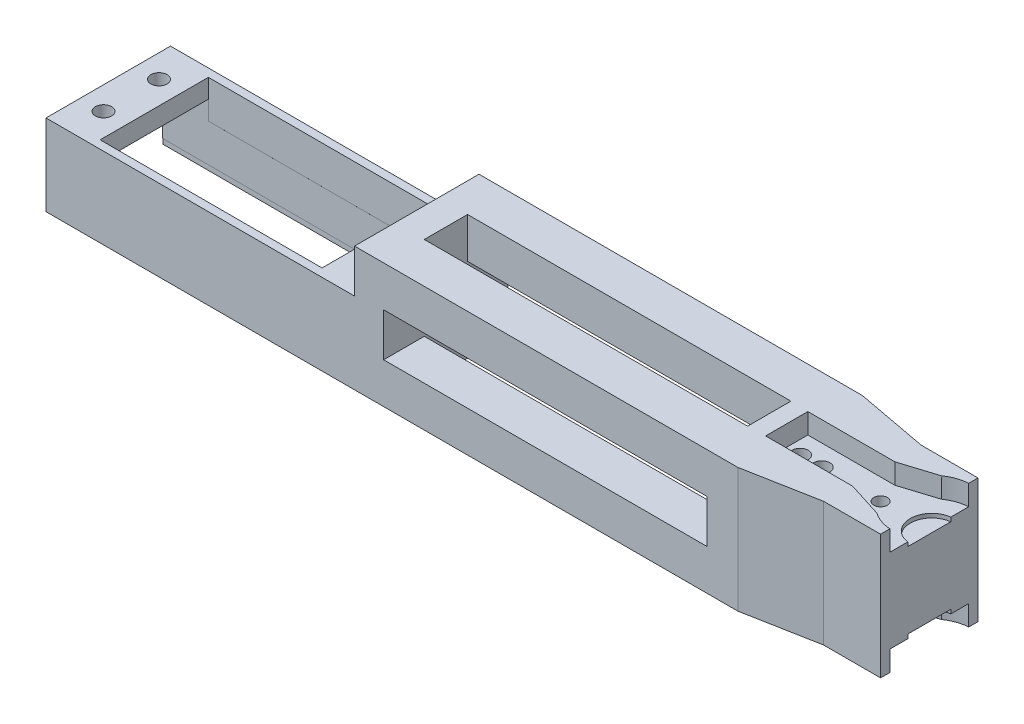
SolidWorks part; units mm, degrees
note: The reader was unsure of these and kept them because the rebuilt part matched: shared geometry of "Sketch1<13>", "Sketch1<14>", "Sketch9<12>".
ref_plane "Front Plane" through (0, 0, 0) normal (0, 0, 1) x (1, 0, 0)
ref_plane "Top Plane" through (0, 0, 0) normal (0, 1, 0) x (1, 0, 0)
ref_plane "Right Plane" through (0, 0, 0) normal (1, 0, 0) x (0, 0, -1)
sketch "Sketch1" plane through (0, 0, 0) normal (0, 1, 0) x (1, 0, 0)
  line L0 (0, 0) -> (14.6038, 0) construction
  line L1 (14.6038, 0) -> (-20.0982, 0) construction
  line L2 (14.6038, -7.2) -> (14.6038, 7.2) construction
  line L3 (-661.2792, -270.937) -> (-113.9458, -270.937) construction
  line L4 (3.082, 5.9567) -> (3.082, -8.253) construction
  line L5 (-17.0385, 7.2) -> (-17.0385, 4.8714) construction
  line L6 (-13.0385, 7.2) -> (-13.0385, 4.8714) construction
  line L7 (6.8243, 9.0002) -> (6.8243, -9.0002)
  line L8 (6.8276, 9.1929) -> (-2.1724, 9.1929) construction
  line L9 (-24.868, 11.5) -> (-24.868, -11.5)
  line L10 (-3.4224, -3.9) -> (-3.4224, 3.9) construction
  line L11 (6.8243, 0.0002) -> (6.8243, 9.0002) construction
  line L12 (6.8243, 0.0002) -> (6.8243, -9.0002) construction
  line L15 (-3.4224, 3.9) -> (3.082, 5.9567)
  line L16 (-3.4224, -3.9) -> (3.082, -5.9567)
  line L17 (-3.4224, 3.9) -> (-19.5134, 3.9)
  line L18 (-19.5134, 3.9) -> (-19.5134, -3.9)
  line L19 (-17.0385, 11.5) -> (-24.868, 11.5)
  line L20 (-19.5134, -3.9) -> (-3.4224, -3.9)
  line L21 (6.8243, 9.0002) -> (-3.6905, 9.0002)
  line L22 (6.8243, -9.0002) -> (-3.6905, -9.0002)
  line L23 (-17.0385, -11.5) -> (-17.0385, 11.5) construction
  line L27 (-3.6905, 9.0002) -> (-17.0385, 11.5)
  line L28 (-3.6905, -9.0002) -> (-17.0385, -11.5)
  line L30 (-24.868, -11.5) -> (-17.0385, -11.5)
  arc A0 (6.8243, 3.9714) -> (6.8243, -3.9714) centre (7.3019, 0) ccw
  circle A1 centre (-17.0385, 0) radius 1.5
  circle A2 centre (-13.0385, 0) radius 1.5
  circle A3 centre (-2.1724, 0) radius 1.25
  arc A4 (6.8243, 7.2844) -> (3.082, 5.9567) centre (7.3019, 0) ccw
  arc A5 (3.082, -5.9567) -> (6.8243, -7.2844) centre (7.3019, 0) ccw
  point P17 (-17.0385, 6.0357)
  point P41 (-3.4224, 0)
  dimension "D4" = 8
  dimension "D5" = 3
  dimension "D7" = 3
  dimension "D10" = 2.5
  dimension "D11" = 14.6
  dimension "D2" = 14.4
  dimension "D3" = 7.8
  dimension "D6" = 4
  dimension "D8" = 9
  dimension "D12" = 9
  dimension "D13" = 3.9
extrude "Boss-Extrude1" add sketch "Sketch1" along normal mid plane 23 contours A5 L16 L20 L18 L17 L15 A4 L7 L21 L27 L19 L9 L30 L28 L22
extrude "Boss-Extrude2" add sketch "Sketch1<13>" along normal mid plane 15.5 contours L16 A5 L7 A0 A4 L15 L17 L18 L20 A3 A2 A1
sketch "Sketch1<13>" plane through (0, 0, 0) normal (0, 1, 0) x (1, 0, 0) same geometry as "Sketch1"
extrude "Boss-Extrude3" add sketch "Sketch1<14>" along normal mid plane 14 contours L7 A0
sketch "Sketch1<14>" plane through (0, 0, 0) normal (0, 1, 0) x (1, 0, 0) same geometry as "Sketch1"
sketch "Sketch2" plane through (-24.868, 0, 0) normal (-1, 0, 0) x (0, 0, 1)
  line L1 (-11.5, -11.5) -> (11.5, -11.5)
  line L2 (-11.5, -11.5) -> (-11.5, 11.5)
  line L3 (-11.5, 11.5) -> (11.5, 11.5)
  line L4 (11.5, -11.5) -> (11.5, 11.5)
extrude "Boss-Extrude4" add sketch "Sketch2" along normal blind 120
sketch "Sketch3" plane through (0, 11.5, 0) normal (0, 1, 0) x (1, 0, 0)
  line L0 (-19.5134, 0) -> (-144.868, 0) construction
  line L1 (-19.5134, 3.9) -> (-19.5134, -3.9) construction
  line L2 (-144.868, -11.5) -> (-144.868, 11.5) construction
sketch "Sketch4" plane through (-144.868, 0, 0) normal (-1, 0, 0) x (0, 0, 1)
  line L0 (0.1956, 11.5) -> (0, -11.5) construction
  line L2 (-11.5, -11.5) -> (11.5, -11.5) construction
  line L3 (11.5, 0) -> (-11.5, 0) construction
  line L4 (11.5, -11.5) -> (11.5, 11.5) construction
  line L5 (-11.5, 11.5) -> (-11.5, -11.5) construction
sketch "Sketch5" plane through (0, 0, 11.5) normal (0, 0, 1) x (1, 0, 0)
  line L0 (-144.868, 0) -> (-17.0385, 0) construction
  line L1 (-144.868, 11.5) -> (-144.868, -11.5) construction
  line L2 (-17.0385, 11.5) -> (-17.0385, -11.5) construction
sketch "Sketch8" plane through (0, -11.5, 0) normal (0, -1, 0) x (1, 0, 0)
  line L0 (-144.868, 11.5) -> (-90.868, 11.5) construction
  line L1 (-144.868, 11.5) -> (-17.0385, 11.5) construction
  line L2 (-144.868, 11.5) -> (-144.868, 10) construction
  line L3 (-144.868, 11.5) -> (-144.868, -11.5) construction
  line L4 (-19.5137, 0.2946) -> (-86.8721, 0.1363) construction
  line L5 (-144.8139, -11.4999) -> (-144.821, -9.9999) construction
  line L6 (-86.8721, 10) -> (-95.3721, 10) construction
  line L7 (-136.368, 10) -> (-86.8721, 10) construction
  line L8 (-144.868, 10) -> (-144.821, -9.9999) construction
  line L9 (-144.821, -9.9999) -> (-86.8721, -9.9999) construction
  line L10 (-86.8721, 10) -> (-86.8721, -9.9999) construction
  line L11 (-144.868, 10) -> (-136.368, 10) construction
  line L12 (-144.868, 10) -> (-144.868, -9.9999) construction
  line L13 (-144.868, -9.9999) -> (-136.368, -9.9999) construction
  line L14 (-136.368, 10) -> (-136.368, -9.9999) construction
  line L15 (-95.3721, 10) -> (-95.3721, -9.9999) construction
  line L16 (-95.3721, -9.9999) -> (-86.8721, -9.9999) construction
  line L17 (-86.8721, -9.9999) -> (-86.8721, 10) construction
  line L18 (-144.8445, 0.0001) -> (-144.868, 0) construction
  line L19 (-86.8721, 10) -> (-95.3721, 10)
  line L20 (-136.368, 0) -> (-144.868, 0) construction
  line L21 (-95.3721, 0) -> (-86.8721, 0.1363) construction
  line L22 (-140.618, 0) -> (-140.618, 2.25) construction
  line L23 (-140.618, 10) -> (-140.618, 8) construction
  line L24 (-140.618, 0) -> (-140.618, -2.25) construction
  line L25 (-140.618, -10) -> (-140.618, -8) construction
  line L26 (-140.618, 2.25) -> (-140.618, 8) construction
  line L27 (-140.618, -8) -> (-140.618, -2.25) construction
  line L28 (-95.3721, 11.5) -> (-95.3721, 10) construction
  line L29 (-144.868, 10) -> (-95.368, 9.9931) construction
  line L30 (-95.3721, 10) -> (-95.368, 9.9931) construction
  line L31 (-95.3721, 10) -> (-86.8721, 10) construction
  line L32 (-95.3721, 10) -> (-95.3721, -9.9999) construction
  line L33 (-95.3721, -9.9999) -> (-86.8721, -9.9999) construction
  line L34 (-86.8721, 10) -> (-86.8721, -9.9999) construction
  line L35 (-95.3721, -9.9999) -> (-86.8721, -9.9999)
  line L36 (-86.8721, 0.0001) -> (-95.3721, 0) construction
  line L37 (-91.1221, 0.0001) -> (-91.1221, 2.2501) construction
  line L38 (-91.1221, 10) -> (-91.1221, 8) construction
  line L39 (-91.1221, 0.0001) -> (-91.122, -2.2499) construction
  line L40 (-91.1218, -9.9999) -> (-91.1219, -7.9999) construction
  line L41 (-91.1221, 2.2501) -> (-91.1221, 8) construction
  line L42 (-91.1219, -7.9999) -> (-91.122, -2.2499) construction
  line L43 (-136.368, 0) -> (-128.868, 0) construction
  line L44 (-86.8721, -9.9999) -> (-144.8139, -9.9999)
  line L45 (-86.8721, -9.9999) -> (-86.8721, -11.4999)
  line L46 (-86.8721, -11.4999) -> (-144.8139, -11.4999)
  line L47 (-144.8139, -9.9999) -> (-144.8139, -11.4999)
  line L48 (-86.8721, 10) -> (-144.868, 10)
  line L49 (-86.8721, 10) -> (-86.8721, 11.5)
  line L50 (-86.8721, 11.5) -> (-144.868, 11.5)
  line L51 (-144.868, 10) -> (-144.868, 11.5)
  line L52 (-19.5134, 0) -> (-144.868, 0) construction
  line L53 (-136.368, -9.9999) -> (-144.868, -9.9999)
  line L55 (-136.368, 10) -> (-95.3721, 10)
  line L56 (-136.368, 10) -> (-136.368, -9.9999)
  line L57 (-136.368, -9.9999) -> (-95.3721, -9.9999)
  line L58 (-95.3721, 10) -> (-95.3721, -9.9999)
  line L59 (-144.868, 10) -> (-136.368, 10)
  line L60 (-144.868, 10) -> (-144.868, -9.9999)
  line L61 (-144.868, -9.9999) -> (-136.368, -9.9999)
  line L62 (-136.368, 10) -> (-136.368, -9.9999)
  line L63 (-95.3721, 10) -> (-86.8721, 10)
  line L64 (-95.3721, 10) -> (-95.3721, -9.9999)
  line L65 (-95.3721, -9.9999) -> (-86.8721, -9.9999)
  line L66 (-86.8721, 10) -> (-86.8721, -9.9999)
  circle A0 centre (-140.618, 5.125) radius 1.5
  circle A1 centre (-140.618, -5.125) radius 1.5
  circle A2 centre (-91.1221, 5.125) radius 1.5
  circle A3 centre (-91.122, -5.1249) radius 1.5
  dimension "D7" = 3
  dimension "D12" = 3
  dimension "D1" = 54
  dimension "D2" = 1.5
  dimension "D3" = 8.5
  dimension "D4" = 41
  dimension "D5" = 2.25
  dimension "D6" = 2
  dimension "D8" = 1.5
  dimension "D9" = 8.5
  dimension "D10" = 2.25
  dimension "D11" = 2
  dimension "D13" = 7.5
sketch "Sketch9" plane through (-144.868, 0, 0) normal (-1, 0, 0) x (0, 0, 1)
  line L0 (11.5, 0) -> (11.5, 3.5) construction
  line L1 (11.5, -11.5) -> (11.5, 11.5) construction
  line L2 (0, -11.5) -> (0.1956, 11.5) construction
  line L7 (11.5, 3.5) -> (10, 3.5)
  line L9 (11.5, -11.5) -> (10, -11.5)
  line L12 (-9.9998, 3.5396) -> (-10, 3.5)
  line L17 (11.5, 3.5) -> (11.5, 0)
  line L21 (-11.4983, -11.3044) -> (-9.9986, -11.3299)
  line L23 (11.5, 11.5) -> (11.5, 3.5455)
  line L26 (11.5, -11.5) -> (10, -11.5)
  line L27 (11.5, 11.5) -> (-11.5, 11.5) construction
  line L31 (-9.9998, 11.5) -> (10, 11.5)
  line L39 (11.5, 0) -> (11.5, -3.5)
  line L42 (11.5, -11.5) -> (11.5, -3.5)
  line L43 (-9.9986, -11.3299) -> (10, -11.3299)
  line L44 (-9.9986, -11.3299) -> (-9.9986, 0.1701)
  line L45 (-9.9986, 0.1701) -> (10, 0.1701)
  line L46 (10, -11.3299) -> (10, 0.1701)
  line L47 (-11.5, 0) -> (11.5, 0)
  line L48 (-11.5, 0) -> (-11.5, 3.5)
  line L49 (-11.5, 3.5) -> (11.5, 3.5)
  line L50 (11.5, 0) -> (11.5, 3.5)
  line L51 (11.5, 11.5) -> (-11.5, 11.5)
  line L52 (11.5, 11.5) -> (11.5, 3.5)
  line L53 (11.5, 3.5) -> (-11.5, 3.5)
  line L54 (-11.5, 11.5) -> (-11.5, 3.5)
  dimension "D1" = 3.5
  dimension "D2" = 1.5
  dimension "D3" = 1.5
  dimension "D4" = 11.5
  dimension "D5" = 3.5
  dimension "D6" = 3.5
extrude "Cut-Extrude7" cut sketch "Sketch9" against normal blind 57 and the other way blind 5 contours L47 L44 L43 L46
extrude "Cut-Extrude8" cut sketch "Sketch8" against normal blind 20 from offset 8 contours L58 L48 L56 L44 | A2 | A3 | A0 | A1 offset against normal yes
sketch "Sketch10" plane through (0, -11.5, 0) normal (0, -1, 0) x (1, 0, 0)
  line L0 (-144.868, -11.5) -> (-144.868, 11.5) construction
  line L2 (-87.6852, 10.2819) -> (-144.868, 10.2819)
  line L3 (-87.6852, 10.2819) -> (-87.6852, -10.0978)
  line L4 (-87.6852, -10.0978) -> (-144.868, -10.0978)
  line L5 (-144.868, 10.2819) -> (-144.868, -10.0978)
  dimension "D1" = 20.3797
extrude "Cut-Extrude9" cut sketch "Sketch10" against normal blind 1
sketch "Sketch11" plane through (0, 11.5, 0) normal (0, 1, 0) x (1, 0, 0)
  line L0 (-82.4806, 11.5) -> (-82.4806, -11.5) construction
  line L1 (-17.0385, 11.5) -> (-144.868, 11.5) construction
  line L2 (-144.868, -11.5) -> (-17.0385, -11.5) construction
  line L3 (-22.7416, 11.5) -> (-22.7416, -11.5) construction
  line L4 (-82.4806, -4) -> (-82.4806, 4)
  line L5 (-82.4806, 0) -> (-22.7416, 0) construction
  line L6 (-52.6111, 0) -> (-52.6111, 11.5) construction
  line L7 (-22.7416, -4) -> (-22.7416, 4)
  line L8 (-82.4806, 4) -> (-22.7416, 4)
  line L9 (-22.7416, -4) -> (-82.4806, -4)
  dimension "D1" = 4
sketch "Sketch12" plane through (0, 0, -11.5) normal (0, 0, -1) x (-1, 0, 0)
  line L0 (87.84, 11.5) -> (82.4806, 11.5) construction
  line L1 (17.0385, 11.5) -> (144.868, 11.5) construction
  line L2 (82.4806, 11.5) -> (82.4806, -11.5) construction
  line L3 (17.0385, -11.5) -> (144.868, -11.5) construction
  line L4 (22.7416, 11.5) -> (22.7416, -11.5) construction
  line L5 (82.4806, 0) -> (22.7416, 0) construction
  line L6 (52.6111, 0) -> (52.6111, -11.5) construction
  line L7 (82.4806, 4) -> (82.4806, -4)
  line L8 (22.7416, 4) -> (22.7416, -4)
  line L9 (82.4806, -4) -> (22.7416, -4)
  line L10 (22.7416, 4) -> (82.4806, 4)
  dimension "D1" = 4
extrude "Cut-Extrude10" cut sketch "Sketch11" against normal blind 40
extrude "Cut-Extrude11" cut sketch "Sketch12" against normal blind 40
extrude "Cut-Extrude12" cut sketch "Sketch9<12>" against normal blind 57
sketch "Sketch9<12>" plane through (-144.868, 0, 0) normal (-1, 0, 0) x (0, 0, 1) same geometry as "Sketch9"
